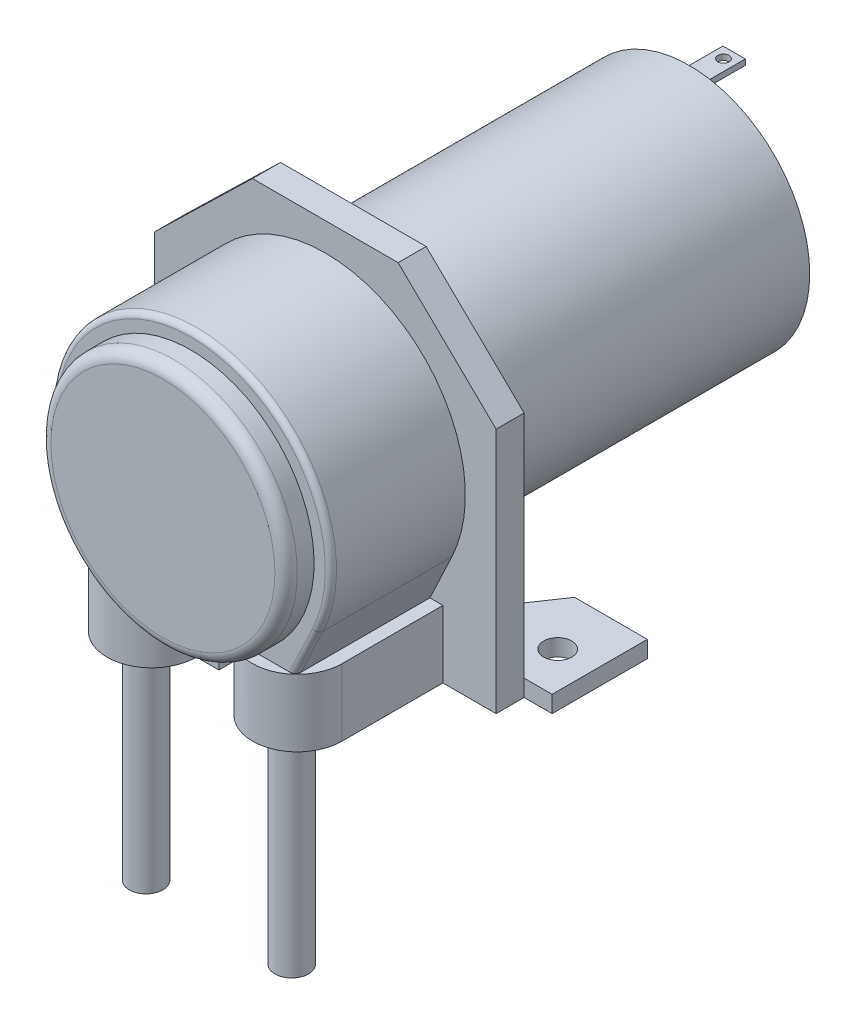
SolidWorks part; units mm, degrees
ref_plane "Front Plane" through (0, 0, 0) normal (0, 0, 1) x (1, 0, 0)
ref_plane "Top Plane" through (0, 0, 0) normal (0, 1, 0) x (1, 0, 0)
ref_plane "Right Plane" through (0, 0, 0) normal (1, 0, 0) x (0, 0, -1)
sketch "Sketch1" plane through (0, 0, 0) normal (0, 0, 1) x (1, 0, 0)
  line L0 (0, 0) -> (0, 38.735) construction
  line L2 (-19.3675, 27.94) -> (-19.3675, 0)
  line L3 (-19.3675, 0) -> (19.3675, 0)
  line L4 (19.3675, 27.94) -> (19.3675, 0)
  line L5 (-8.255, 38.735) -> (8.255, 38.735)
  line L6 (-19.3675, 27.94) -> (-8.255, 38.735)
  line L7 (8.255, 38.735) -> (19.3675, 27.94)
  point P9 (0, 0)
  dimension "D1" = 38.735
  dimension "D2" = 16.51
  dimension "D3" = 38.735
  dimension "D4" = 27.94
extrude "Boss-Extrude1" add sketch "Sketch1" along normal blind 3.175
sketch "Sketch2" plane through (0, 0, 3.175) normal (0, 0, 1) x (1, 0, 0)
  line L0 (-13.335, 0) -> (13.335, 0) construction
  line L1 (-19.3675, 0) -> (19.3675, 0) construction
  line L3 (-13.335, 0) -> (-3.175, 0)
  line L4 (-13.335, 0) -> (-13.335, 7.62)
  line L5 (-13.335, 7.62) -> (-3.175, 7.62)
  line L6 (-3.175, 0) -> (-3.175, 7.62)
  line L7 (13.335, 0) -> (3.175, 0)
  line L8 (13.335, 0) -> (13.335, 7.62)
  line L9 (13.335, 7.62) -> (3.175, 7.62)
  line L10 (3.175, 0) -> (3.175, 7.62)
  dimension "D1" = 26.67
  dimension "D2" = 7.62
  dimension "D3" = 10.16
extrude "Boss-Extrude2" add sketch "Sketch2" along normal blind 11.43
sketch "Sketch3" plane through (0, 0, 14.605) normal (0, 0, 1) x (1, 0, 0)
  line L0 (-8.255, 7.62) -> (-8.255, 0)
  line L4 (-13.335, 7.62) -> (-13.335, 0)
  line L5 (-13.335, 0) -> (-3.175, 0)
  line L6 (-3.175, 0) -> (-3.175, 7.62)
  line L7 (-3.175, 7.62) -> (-13.335, 7.62)
  line L8 (-13.335, 7.62) -> (-13.335, 0)
  line L9 (-13.335, 0) -> (-8.255, 0)
  line L11 (-8.255, 7.62) -> (-13.335, 7.62)
  dimension "D1" = 0
revolve "Revolve1" add sketch "Sketch3" angle 180 about L0 reverse direction yes
sketch "Sketch4" plane through (0, 0, 14.605) normal (0, 0, 1) x (1, 0, 0)
  line L0 (13.335, 7.62) -> (3.175, 7.62) construction
  line L1 (8.255, 7.62) -> (3.175, 7.62)
  line L2 (8.255, 7.62) -> (8.255, 0)
  line L3 (8.255, 0) -> (3.175, 0)
  line L4 (3.175, 7.62) -> (3.175, 0)
revolve "Revolve2" add sketch "Sketch4" angle 180 about L2 reverse direction yes
sketch "Sketch5" plane through (0, 0, 3.175) normal (0, 0, 1) x (1, 0, 0)
  line L0 (0, 38.735) -> (0, 0) construction
  line L1 (8.255, 38.735) -> (-8.255, 38.735) construction
  line L2 (-11.5234, 35.56) -> (11.5234, 35.56) construction
  line L3 (-8.255, 38.735) -> (-19.3675, 27.94) construction
  line L4 (19.3675, 27.94) -> (8.255, 38.735) construction
  line L5 (-19.3675, 3.81) -> (19.3675, 3.81) construction
  line L6 (-19.3675, 0) -> (-13.335, 0) construction
  line L7 (-13.335, 0) -> (-3.175, 0) construction
  line L8 (-14.3527, 12.9014) -> (-10.0557, 3.81)
  line L9 (19.3675, 0) -> (19.3675, 27.94) construction
  line L10 (-19.3675, 27.94) -> (-19.3675, 0) construction
  line L11 (-14.3527, 12.9014) -> (-8.255, 0) construction
  line L12 (-10.0557, 3.81) -> (10.0557, 3.81)
  line L13 (14.3527, 12.9014) -> (8.255, 0) construction
  line L14 (10.0557, 3.81) -> (14.3527, 12.9014)
  line L15 (0, 0) -> (-8.255, 0)
  line L16 (0, 0) -> (8.255, 0)
  arc A0 (14.3527, 12.9014) -> (-14.3527, 12.9014) centre (0, 19.685) ccw
  point P20 (0, 3.81)
  line M19 (-13.335, 7.62) -> (-3.175, 7.62)
  line M20 (-3.175, 7.62) -> (-3.175, 0)
  line M22 (3.175, 0) -> (3.175, 7.62)
  line M23 (3.175, 7.62) -> (13.335, 7.62)
  dimension "D1" = 31.75
  dimension "D2" = 3.175
  dimension "D3" = 3.81
extrude "Boss-Extrude3" add sketch "Sketch5" along normal blind 15.24 contours L14 A0 L8 L12 M19 M20 M22 M23 region at (0, 20.1285, 3.175)
sketch "Sketch6" plane through (0, 0, 18.415) normal (0, 0, 1) x (1, 0, 0)
  circle A0 centre (0, 19.685) radius 13.97
  arc A1 (14.3527, 12.9014) -> (-14.3527, 12.9014) centre (0, 19.685) ccw construction
  dimension "D1" = 27.94
extrude "Boss-Extrude4" add sketch "Sketch6" along normal blind 3.175
fillet "Fillet1" radius 1.27 1 edges at (13.97, 19.685, 21.59)
fillet "Fillet2" radius 0.635 3 edges at (13.1046, 10.2607, 18.415) (-13.1046, 10.2607, 18.415) (0, 35.56, 18.415)
sketch "Sketch8" plane through (0, 0, 0) normal (0, -1, 0) x (1, 0, 0)
  line L0 (0, 0) -> (-22.5425, 0) construction
  line L1 (-22.5425, 0) -> (-22.5425, -10.795)
  line L2 (-22.5425, -10.795) -> (-14.2875, -10.795)
  line L3 (-14.2875, -10.795) -> (-6.985, 0)
  line L6 (-22.5425, 0) -> (-6.985, 0)
  line L7 (-19.3675, 3.175) -> (-19.3675, 0) construction
  line L8 (0, 0) -> (0, 19.9559) construction
  line L9 (22.5425, -10.795) -> (14.2875, -10.795)
  line L10 (22.5425, 0) -> (22.5425, -10.795)
  line L11 (22.5425, 0) -> (6.985, 0)
  line L12 (14.2875, -10.795) -> (6.985, 0)
  dimension "D1" = 6.985
  dimension "D2" = 3.175
  dimension "D3" = 10.795
  dimension "D4" = 8.255
extrude "Boss-Extrude5" add sketch "Sketch8" against normal blind 1.905
sketch "Sketch9" plane through (0, 0, 0) normal (0, -1, 0) x (1, 0, 0)
  line L0 (20.0025, -4.7625) -> (-20.0025, -4.7625) construction
  line L1 (0, 0) -> (0, -4.7625) construction
  line L2 (-6.985, 0) -> (6.985, 0) construction
  line L3 (18.415, -3.175) -> (18.415, 3.175) construction
  line L7 (13.335, 3.175) -> (19.3675, 3.175) construction
  circle A0 centre (18.415, -4.7625) radius 1.5875
  circle A1 centre (-18.415, -4.7625) radius 1.5875
  dimension "D2" = 3.175
  dimension "D1" = 40.005
  dimension "D3" = 6.35
extrude "Cut-Extrude1" cut sketch "Sketch9" against normal through all
sketch "Sketch11" plane through (0, 0, 0) normal (0, -1, 0) x (1, 0, 0)
  line L4 (-11.43, 6.985) -> (-5.08, 6.985)
  line L5 (0, 0) -> (0, 22.7679) construction
  line L6 (-5.08, 3.175) -> (-5.08, 14.605)
  line L7 (-11.43, 14.605) -> (-11.43, 3.175)
  line L8 (-5.08, 6.985) -> (-5.08, 14.605)
  line L9 (-11.43, 14.605) -> (-11.43, 6.985)
  line L10 (11.43, 14.605) -> (11.43, 6.985)
  line L11 (5.08, 6.985) -> (5.08, 14.605)
  line L12 (11.43, 6.985) -> (5.08, 6.985)
  arc A4 (5.08, 14.605) -> (11.43, 14.605) centre (8.255, 14.605) cw
  arc A5 (-5.08, 14.605) -> (-11.43, 14.605) centre (-8.255, 14.605) ccw
  arc A6 (-5.08, 14.605) -> (-11.43, 14.605) centre (-8.255, 14.605) ccw
  dimension "D2" = 7.62
  dimension "D1" = 1.905
extrude "Cut-Extrude2" cut sketch "Sketch11" against normal blind 1.27
sketch "Sketch10" plane through (0, 1.27, 0) normal (0, -1, 0) x (1, 0, 0)
  line L0 (-13.335, 3.175) -> (13.335, 3.175) construction
  line L1 (-8.255, 19.685) -> (-8.255, 3.175) construction
  line L2 (0, 0) -> (0, 32.6297) construction
  arc A0 (-3.175, 14.605) -> (-13.335, 14.605) centre (-8.255, 14.605) ccw construction
  circle A1 centre (-8.255, 15.24) radius 1.905
  circle A2 centre (8.255, 15.24) radius 1.905
  point P11 (-8.255, 13.335)
  dimension "D2" = 3.81
  dimension "D1" = 10.16
extrude "Boss-Extrude6" add sketch "Sketch10" along normal blind 25.4
sketch "Sketch12" plane through (0, 0, 0) normal (0, 0, -1) x (-1, 0, 0)
  circle A0 centre (0, 19.685) radius 13.6525
  circle A1 centre (0, 19.685) radius 12.7 construction
  dimension "D1" = 27.305
extrude "Boss-Extrude7" add sketch "Sketch12" along normal blind 38.1
sketch "Sketch13" plane through (0, 0, -38.1) normal (0, 0, -1) x (-1, 0, 0)
  circle A0 centre (0, 19.685) radius 3.175
  dimension "D1" = 6.35
extrude "Boss-Extrude8" add sketch "Sketch13" along normal blind 2.54
sketch "Sketch14" plane through (0, 0, -38.1) normal (0, 0, -1) x (-1, 0, 0)
  line L0 (0, 33.3375) -> (0, 6.0325) construction
  line L10 (-1.27, 31.4325) -> (1.27, 31.4325)
  line L11 (-1.27, 31.4325) -> (-1.27, 32.0675)
  line L12 (-1.27, 32.0675) -> (1.27, 32.0675)
  line L13 (1.27, 31.4325) -> (1.27, 32.0675)
  line L14 (-1.27, 31.4325) -> (1.27, 32.0675) construction
  line L15 (-1.27, 32.0675) -> (1.27, 31.4325) construction
  line L16 (-1.27, 7.9375) -> (1.27, 7.9375)
  line L17 (-1.27, 7.9375) -> (-1.27, 7.3025)
  line L18 (-1.27, 7.3025) -> (1.27, 7.3025)
  line L19 (1.27, 7.9375) -> (1.27, 7.3025)
  line L20 (-1.27, 7.9375) -> (1.27, 7.3025) construction
  line L21 (-1.27, 7.3025) -> (1.27, 7.9375) construction
  circle A1 centre (0, 19.685) radius 13.6525 construction
  point P4 (0, 31.75)
  point P9 (0, 7.62)
  point P15 (0, 0)
  point P16 (0, 0)
  dimension "D1" = 1.27
  dimension "D2" = 1.27
  dimension "D3" = 2.54
  dimension "D4" = 0.635
extrude "Boss-Extrude9" add sketch "Sketch14" along normal blind 5.08
sketch "Sketch15" plane through (0, 7.3025, 0) normal (0, -1, 0) x (1, 0, 0)
  line L0 (0, -43.18) -> (0, -41.9698) construction
  line L1 (1.27, -43.18) -> (-1.27, -43.18) construction
  circle A0 centre (0, -41.9698) radius 0.635
  point P5 (0.3907, -41.9698)
  point P6 (0, 0)
  dimension "D1" = 1.27
extrude "Cut-Extrude3" cut sketch "Sketch15" against normal through all
